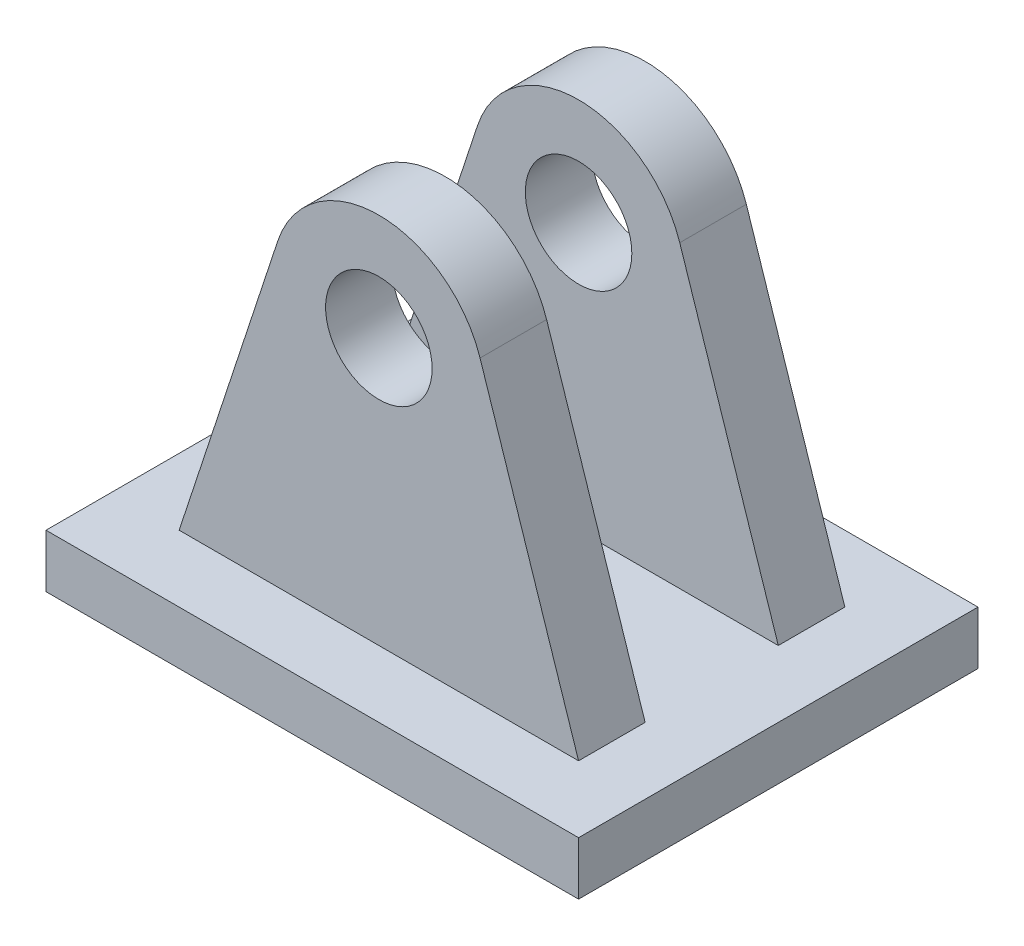
SolidWorks part; units mm, degrees
ref_plane "Piano frontale" through (0, 0, 0) normal (0, 0, 1) x (1, 0, 0)
ref_plane "Piano superiore" through (0, 0, 0) normal (0, 1, 0) x (1, 0, 0)
ref_plane "Piano destro" through (0, 0, 0) normal (1, 0, 0) x (0, 0, -1)
sketch "Sketch1" plane through (0, 0, 0) normal (0, 1, 0) x (1, 0, 0)
  line L1 (-100, -75) -> (100, -75)
  line L2 (-100, -75) -> (-100, 75)
  line L3 (-100, 75) -> (100, 75)
  line L4 (100, -75) -> (100, 75)
  line L5 (-100, -75) -> (100, 75) construction
  line L6 (-100, 75) -> (100, -75) construction
  point P0 (0, 0)
  dimension "D1" = 200
  dimension "D2" = 150
extrude "Boss-Extrude1" add sketch "Sketch1" along normal blind 20
sketch "Sketch3" plane through (0, 0, 0) normal (0, 0, 1) x (1, 0, 0)
  line L0 (-37.9974, 132.498) -> (-75, 20)
  line L1 (-100, 20) -> (100, 20) construction
  line L2 (37.9974, 132.498) -> (75, 20)
  line L3 (-75, 20) -> (75, 20)
  arc A0 (37.9974, 132.498) -> (-37.9974, 132.498) centre (0, 120) ccw
  dimension "D2" = 40
  dimension "D1" = 150
  dimension "D3" = 100
extrude "Boss-Extrude2" add sketch "Sketch3" along normal mid plane 100
sketch "Sketch5" plane through (0, 0, 0) normal (0, 0, 1) x (1, 0, 0)
  line L3 (-37.9974, 132.498) -> (-75, 20)
  line L4 (-75, 20) -> (75, 20)
  line L5 (75, 20) -> (37.9974, 132.498)
  line L6 (-37.9974, 132.498) -> (-75, 20)
  line L7 (-75, 20) -> (75, 20)
  line L8 (75, 20) -> (37.9974, 132.498)
  arc A1 (37.9974, 132.498) -> (-37.9974, 132.498) centre (0, 120) ccw
  arc A2 (37.9974, 132.498) -> (-37.9974, 132.498) centre (0, 120) ccw
  dimension "D1" = 0
extrude "Cut-Extrude1" cut sketch "Sketch5" against normal mid plane 50
sketch "Sketch6" plane through (0, 0, 50) normal (0, 0, 1) x (1, 0, 0)
  circle A0 centre (0, 120) radius 20
  dimension "D1" = 40
extrude "Cut-Extrude2" cut sketch "Sketch6" against normal through all
ref_axis "Axis1" through (0, 120, 25) along (0, 0, 1)
